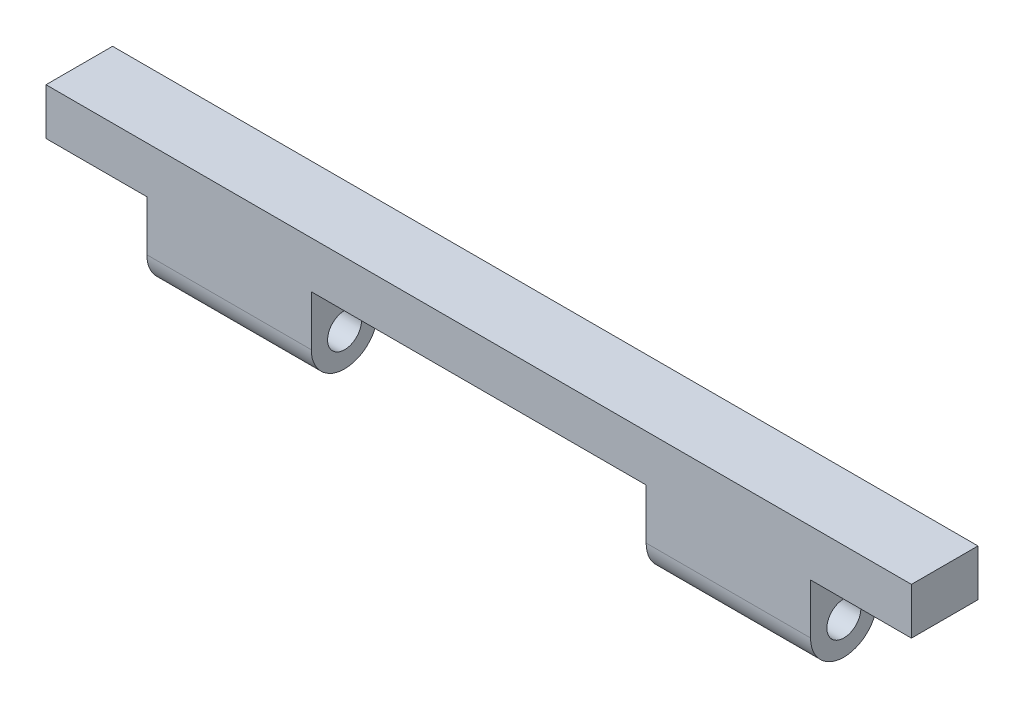
SolidWorks part; units mm, degrees
ref_plane "Front Plane" through (0, 0, 0) normal (0, 0, 1) x (1, 0, 0)
ref_plane "Top Plane" through (0, 0, 0) normal (0, 1, 0) x (1, 0, 0)
ref_plane "Right Plane" through (0, 0, 0) normal (1, 0, 0) x (0, 0, -1)
sketch "Sketch1" plane through (0, 0, 0) normal (0, 0, 1) x (1, 0, 0)
  line L0 (0, -55) -> (0, 55) construction
  line L1 (-56.15, -11) -> (49.85, -11)
  line L2 (-65, 1.55) -> (-65, 8.55)
  line L3 (-65, 8.55) -> (65, 8.55)
  line L4 (65, 1.55) -> (65, 8.55)
  line L5 (-56.15, -7.3859) -> (65, 8.55) construction
  line L6 (-65, 8.55) -> (56.15, -7.3859) construction
  line L11 (-56.15, -11) -> (-49.85, -11)
  line L12 (-56.15, -11) -> (-56.15, 1.55)
  line L13 (-56.15, 1.55) -> (-49.85, 1.55)
  line L14 (-49.85, -11) -> (-49.85, 1.55)
  line L15 (56.15, 1.55) -> (49.85, 1.55)
  line L16 (49.85, -11) -> (49.85, 1.55)
  line L17 (56.15, -11) -> (49.85, -11)
  line L18 (56.15, -11) -> (56.15, 1.55)
  line L19 (49.85, -11) -> (56.15, -11)
  line L22 (-56.15, 1.55) -> (-65, 1.55)
  line L23 (56.15, 1.55) -> (65, 1.55)
  line L24 (16.85, 0) -> (25.15, 0)
  line L25 (-16.85, -11) -> (-25.15, -11)
  line L26 (-16.85, -11) -> (-16.85, 0)
  line L27 (-16.85, 0) -> (-25.15, 0)
  line L28 (-25.15, -11) -> (-25.15, 0)
  line L29 (25.15, -11) -> (25.15, 0)
  line L30 (16.85, -11) -> (25.15, -11)
  line L31 (16.85, -11) -> (16.85, 0)
  line L32 (-25.15, 0) -> (-25.15, 1.55)
  line L33 (25.15, 1.55) -> (-25.15, 1.55)
  line L36 (25.15, 0) -> (25.15, 1.55)
  point P0 (0, 0)
  dimension "D8" = 11
  dimension "D2" = 130
  dimension "D3" = 24.7
  dimension "D4" = 12.55
  dimension "D5" = 6.3
  dimension "D6" = 8.3
  dimension "D7" = 49.85
  dimension "D11" = 7
extrude "Boss-Extrude1" add sketch "Sketch1" along normal mid plane 10 contours L27 L24 L29 L1 L16 L15 L23 L4 L3 L2 L22 L13 L14 L28 region at (-48.5354, -4.725, 0)
sketch "Sketch2" plane through (-65, 0, 0) normal (-1, 0, 0) x (0, 0, 1)
  line L0 (5, -11) -> (-5, -11) construction
  circle A0 centre (0, -5.95) radius 2.55
  dimension "D1" = 5.1
  dimension "D2" = 5.05
extrude "Cut-Extrude1" cut sketch "Sketch2" against normal through all
fillet "Fillet1" radius 5 4 edges at (37.5, -11, 5) (37.5, -11, -5) (-37.5, -11, 5) (-37.5, -11, -5) tangent propagation no
